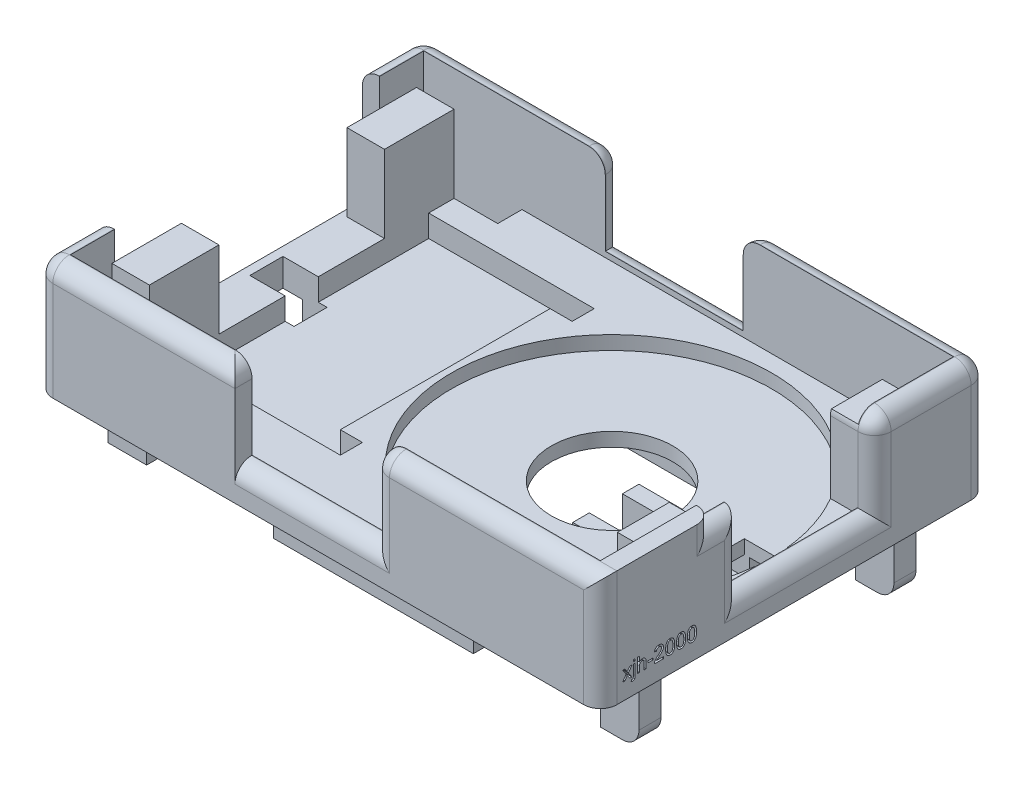
SolidWorks part; units mm, degrees
note: The reader was unsure of these and kept them because the rebuilt part matched: shared geometry of "草图1<4>".
material "PP 共聚物"
ref_plane "前视基准面" through (0, 0, 0) normal (0, 0, 1) x (1, 0, 0)
ref_plane "上视基准面" through (0, 0, 0) normal (0, 1, 0) x (1, 0, 0)
ref_plane "右视基准面" through (0, 0, 0) normal (1, 0, 0) x (0, 0, -1)
sketch "草图1" plane through (0, 0, 0) normal (0, 1, 0) x (1, 0, 0)
  line L5 (48.1, -32.1) -> (-48.1, -32.1)
  line L6 (48.1, -32.1) -> (48.1, 32.1)
  line L7 (48.1, 32.1) -> (-48.1, 32.1)
  line L8 (-48.1, -32.1) -> (-48.1, 32.1)
  line L9 (48.1, -32.1) -> (-48.1, 32.1) construction
  line L10 (48.1, 32.1) -> (-48.1, -32.1) construction
  point P0 (0, 0)
  dimension "D1" = 96.2
  dimension "D2" = 64.2
extrude "凸台-拉伸1基本面" add sketch "草图1" along normal blind 5 contours L6 L5 L8 L7
sketch "超声空间" plane through (0, 0, 0) normal (0, -1, 0) x (1, 0, 0)
  line L1 (-50.5, 24) -> (-44.5, 24)
  line L2 (-50.5, 24) -> (-50.5, -24)
  line L3 (-50.5, -24) -> (-44.5, -24)
  line L4 (-44.5, 24) -> (-44.5, -24)
  line L5 (-59.6476, 0) -> (64.1438, 0) construction
  dimension "D1" = 48
  dimension "D2" = 6
sketch "草图4" plane through (0, 0, 0) normal (0, 1, 0) x (1, 0, 0)
  line L0 (-71.4213, 0) -> (77.6532, 0) construction
  line L1 (41.1, 25.1) -> (48.1, 25.1)
  line L2 (-48.1, 25.1) -> (-41.1, 25.1)
  line L3 (-48.1, 25.1) -> (-48.1, 21.1)
  line L4 (-48.1, 21.1) -> (-41.1, 21.1)
  line L5 (-41.1, 25.1) -> (-41.1, 21.1)
  line L6 (41.1, 25.1) -> (41.1, 21.1)
  line L7 (41.1, 21.1) -> (48.1, 21.1)
  line L8 (48.1, 25.1) -> (48.1, 21.1)
  line L9 (48.1, -25.1) -> (48.1, -21.1)
  line L10 (41.1, -21.1) -> (48.1, -21.1)
  line L11 (41.1, -25.1) -> (41.1, -21.1)
  line L12 (-41.1, -25.1) -> (-41.1, -21.1)
  line L13 (-48.1, -21.1) -> (-41.1, -21.1)
  line L14 (-48.1, -25.1) -> (-48.1, -21.1)
  line L15 (-48.1, -25.1) -> (-41.1, -25.1)
  line L16 (41.1, -25.1) -> (48.1, -25.1)
  line L17 (48.1, 32.1) -> (-48.1, 32.1) construction
  line L18 (-48.1, -32.1) -> (-48.1, 32.1) construction
  line L19 (48.1, -32.1) -> (48.1, 32.1) construction
  line L20 (18.1, -25.1) -> (18.1, -21.1)
  line L21 (-18.1, 25.1) -> (18.1, 25.1)
  line L22 (-18.1, 25.1) -> (-18.1, 21.1)
  line L23 (-18.1, 21.1) -> (18.1, 21.1)
  line L24 (18.1, 25.1) -> (18.1, 21.1)
  line L25 (-18.1, -21.1) -> (18.1, -21.1)
  line L26 (-18.1, -25.1) -> (-18.1, -21.1)
  line L27 (-18.1, -25.1) -> (18.1, -25.1)
  dimension "D1" = 4
  dimension "D2" = 7
  dimension "D3" = 23
  dimension "D4" = 23
  dimension "D5" = 7
  dimension "D6" = 7
extrude "凸台-拉伸3-舵机支撑" add sketch "草图4" against normal blind 12
sketch "草图5" plane through (0, 5, 0) normal (0, 1, 0) x (1, 0, 0)
  line L0 (-67.8133, 0) -> (64.4513, 0) construction
  line L2 (-44.9, 27.6) -> (-38.1, 27.6)
  line L3 (-44.9, 27.6) -> (-44.9, 15)
  line L4 (-44.9, 15) -> (-38.1, 15)
  line L5 (-38.1, 27.6) -> (-38.1, 15)
  line L13 (-38.1, -27.6) -> (-38.1, -15)
  line L14 (-44.9, -15) -> (-38.1, -15)
  line L15 (-44.9, -27.6) -> (-44.9, -15)
  line L16 (-44.9, -27.6) -> (-38.1, -27.6)
  line L17 (-48.1, -32.1) -> (-48.1, 32.1) construction
  line L18 (48.1, 32.1) -> (-48.1, 32.1) construction
  line L31 (48.1, -32.1) -> (48.1, 32.1) construction
  line L42 (43.1, -14.6) -> (48.1, -14.6)
  line L43 (48.1, -24) -> (48.1, -14.6)
  line L44 (43.1, -24) -> (48.1, -24)
  line L45 (43.1, -24) -> (43.1, -14.6)
  line L46 (48.1, -32.1) -> (-48.1, -32.1) construction
  line L47 (43.1, 24) -> (43.1, 14.6)
  line L48 (43.1, 24) -> (48.1, 24)
  line L49 (48.1, 24) -> (48.1, 14.6)
  line L50 (43.1, 14.6) -> (48.1, 14.6)
  dimension "D1" = 3.2
  dimension "D2" = 10
  dimension "D3" = 4.5
  dimension "D4" = 30
  dimension "D5" = 5
  dimension "D6" = 9.4
  dimension "D7" = 8.1
extrude "凸台-拉伸4-板子螺丝支撑" add sketch "草图5" along normal blind 14
sketch "草图12" plane through (0, 0, 0) normal (0, -1, 0) x (1, 0, 0)
  line L0 (-56.5877, 0) -> (64.1716, 0) construction
  line L1 (0, 37.482) -> (0, -42.0761) construction
  line L12 (-41, 6) -> (-18, 6)
  line L13 (-41, 6) -> (-41, 3)
  line L14 (-41, 3) -> (-18, 3)
  line L15 (-18, 6) -> (-18, 3)
  line L16 (-41, -3) -> (-18, -3)
  line L17 (-18, -6) -> (-18, -3)
  line L18 (-41, -6) -> (-18, -6)
  line L19 (-41, -6) -> (-41, -3)
  line L20 (17, 6) -> (17, 3)
  line L21 (17, 6) -> (40, 6)
  line L22 (40, 6) -> (40, 3)
  line L23 (17, 3) -> (40, 3)
  line L24 (17, -3) -> (40, -3)
  line L25 (40, -6) -> (40, -3)
  line L26 (17, -6) -> (40, -6)
  line L27 (17, -6) -> (17, -3)
  dimension "D2" = 6
  dimension "D3" = 3
  dimension "D4" = 23
  dimension "D5" = 18
  dimension "D6" = 23
  dimension "D7" = 3
  dimension "D8" = 3
  dimension "D9" = 17
  dimension "D1" = 2
extrude "凸台-拉伸8-理线" add sketch "草图12" along normal blind 10
extrude "拉伸-薄壁" add sketch "草图1<4>" along normal offset from surface (21 mm away) 2 thin up to face at (-41.5, 19, -21.3) offset beyond the face yes thin type two direction wall 3 second wall 0.1
sketch "草图1<4>" plane through (0, 0, 0) normal (0, 1, 0) x (1, 0, 0) same geometry as "草图1"
sketch "草图13" plane through (0, 0, 0) normal (0, -1, 0) x (1, 0, 0)
  line L1 (39.1, 3) -> (47.1, 3)
  line L2 (39.1, 3) -> (39.1, -3)
  line L3 (39.1, -3) -> (47.1, -3)
  line L4 (47.1, 3) -> (47.1, -3)
  line L6 (51.1, 35.1) -> (51.1, -35.1) construction
  line L7 (-58, 0) -> (66.2478, 0) construction
  line L14 (-44.5, 3) -> (-36.5, 3)
  line L15 (-44.5, 3) -> (-44.5, -3)
  line L16 (-44.5, -3) -> (-36.5, -3)
  line L17 (-36.5, 3) -> (-36.5, -3)
  line L18 (-41, 3) -> (-18, 3) construction
  dimension "D1" = 8
  dimension "D2" = 6
  dimension "D3" = 4
  dimension "D4" = 8
extrude "切除-拉伸-理线" cut sketch "草图13" against normal up to next
sketch "草图21" plane through (0, 0, 35.1) normal (0, 0, 1) x (1, 0, 0)
  line L0 (-51.1, 21) -> (51.1, 21) construction
  line L1 (-15.1, 21) -> (9.9, 21)
  line L2 (-15.1, 21) -> (-15.1, 6)
  line L3 (-15.1, 6) -> (9.9, 6)
  line L4 (9.9, 21) -> (9.9, 6)
  line L5 (-51.1, 0) -> (51.1, 0) construction
  line L6 (-51.1, 21) -> (-51.1, 0) construction
  dimension "D1" = 25
  dimension "D2" = 6
  dimension "D3" = 36
extrude "切除-拉伸-侧边红外" cut sketch "草图21" against normal through all
sketch "草图22" plane through (51.1, 0, 0) normal (1, 0, 0) x (0, 0, -1)
  line L0 (-35.1, 21) -> (35.1, 21) construction
  line L1 (-14.6, 21) -> (-14.6, 19)
  line L2 (-14.6, 19) -> (-9.6, 19)
  line L3 (-9.6, 19) -> (-9.6, 6)
  line L4 (-9.6, 6) -> (14.6, 6)
  line L5 (14.6, 6) -> (14.6, 21)
  line L6 (14.6, 21) -> (-14.6, 21)
  line L7 (0, 0) -> (0, 26.7985) construction
  line L8 (-35.1, 0) -> (35.1, 0) construction
  line L9 (35.1, 21) -> (35.1, 0) construction
  line L10 (-35.1, 21) -> (-35.1, 0) construction
  point P16 (-9.6, 12.5)
  dimension "D1" = 20.5
  dimension "D2" = 20.5
  dimension "D3" = 6
  dimension "D4" = 25.5
  dimension "D5" = 2
extrude "切除-拉伸-尾部红外" cut sketch "草图22" against normal up to next
sketch "草图25" plane through (51.1, 0, 0) normal (1, 0, 0) x (0, 0, -1)
  line L0 (-35.1, 21) -> (-35.1, 0) construction
  line L1 (-35.1, 0) -> (35.1, 0) construction
  text T0 "xjh-2000" height in points 10
  point P5 (-30.2298, 8.4333)
  dimension "D1" = 4
  dimension "D2" = 3
extrude "切除-拉伸-自我介绍" cut sketch "草图25" against normal blind 1.5
sketch "草图20" plane through (0, 5, 0) normal (0, 1, 0) x (1, 0, 0)
  line L2 (30.1917, 32) -> (44.5, 32)
  line L3 (30.1917, 32) -> (30.1917, 27.6)
  line L4 (30.1917, 27.6) -> (44.5, 27.6)
  line L5 (44.5, 32) -> (44.5, 27.6)
  line L6 (0, 37.255) -> (0, -43.0013) construction
  line L7 (0, -37.482) -> (0, 42.0761) construction
  line L8 (-58.1518, 0) -> (69.3057, 0) construction
  line L9 (-30.1917, 27.6) -> (-44.5, 27.6)
  line L10 (-44.5, 32) -> (-44.5, 27.6)
  line L11 (-30.1917, 32) -> (-44.5, 32)
  line L12 (-30.1917, 32) -> (-30.1917, 27.6)
  line L13 (30.1917, -27.6) -> (44.5, -27.6)
  line L14 (44.5, -32) -> (44.5, -27.6)
  line L15 (30.1917, -32) -> (44.5, -32)
  line L16 (30.1917, -32) -> (30.1917, -27.6)
  line L17 (-30.1917, -32) -> (-30.1917, -27.6)
  line L18 (-30.1917, -32) -> (-44.5, -32)
  line L19 (-44.5, -32) -> (-44.5, -27.6)
  line L20 (-30.1917, -27.6) -> (-44.5, -27.6)
  line L21 (-44.9, -27.6) -> (-38.1, -27.6) construction
  line L22 (48, -14.6) -> (48, 14.6) construction
  line L23 (48, 32) -> (-48, 32) construction
  line L26 (-38.1, 27.6) -> (-44.9, 27.6) construction
  dimension "D1" = 3.5
  dimension "D4" = 0
extrude "切除-拉伸_舵机插头空间" cut sketch "草图20" against normal up to next
sketch "草图26" plane through (0, 0, 0) normal (0, -1, 0) x (1, 0, 0)
  line L0 (-51.1, -35.1) -> (-51.1, 35.1) construction
  line L1 (-51.1, 24) -> (-46.1, 24)
  line L2 (-51.1, 24) -> (-51.1, -24)
  line L3 (-51.1, -24) -> (-46.1, -24)
  line L4 (-46.1, 24) -> (-46.1, -24)
  line L6 (-59.6476, 0) -> (71.5879, 0) construction
  dimension "D1" = 5
  dimension "D2" = 48
extrude "切除-拉伸-超声空间" cut sketch "草图26" against normal through all and the other way through all
fillet "圆角" radius 3 45 edges at (45.55, 19, -14.6) (-41, -10, 4.5) (-18, -10, 4.5) (-41, -10, -4.5) (-18, -10, -4.5) (17, -10, 4.5) (40, -10, 4.5) (17, -10, -4.5) (40, -10, -4.5) (48.1, 0, 23.1) (48.1, 0, -23.1) (51.1, 10.5, -35.1) (51.1, 10.5, 35.1) (-51.1, 10.5, 35.1) (-51.1, 10.5, -35.1) (30.5, 21, -35.1) (-51.1, 21, -29.55) (-33.1, 21, 35.1) (48.1, -12, -23.1) (-33.1, 21, -35.1) (30.5, 21, 35.1) (9.9, 21, 33.55) (-15.1, 21, 33.55) (-15.1, 21, -33.55) (-2.6, 6, -35.1) (-15.1, 13.5, -35.1) (9.9, 13.5, -35.1) (9.9, 21, -33.55) (44.6, 0, -21.1) (-2.6, 6, 35.1) (9.9, 13.5, 35.1) (48, 20, -14.6) (49.55, 21, -14.6) (51.1, 20, 14.6) (51.1, 19, 12.1) (51.1, 12.5, 9.6) (51.1, 6, -2.5) (51.1, 13.5, -14.6) (48.1, -12, 23.1) (44.6, 0, 21.1) (-43.6, 0, 21.1) (0, 0, -21.1) (-51.1, 21, 29.55) (-43.6, 0, -21.1) (0, 0, 21.1)
sketch "草图27" plane through (0, 5, 0) normal (0, 1, 0) x (1, 0, 0)
  line L0 (-59.6476, 0) -> (72.0758, 0) construction
  line L1 (-59.6476, 0) -> (64.1438, 0) construction
  line L2 (-12.1, -19) -> (-8.1, -19)
  line L3 (-12.1, 23) -> (-8.1, 23)
  line L4 (-38.1, 15) -> (-38.1, 27.6) construction
  line L5 (-38.1, 23) -> (-12.1, 23)
  line L6 (-38.1, 23) -> (-38.1, -23)
  line L7 (-38.1, -23) -> (-12.1, -23)
  line L10 (-12.1, 19) -> (-8.1, 19)
  line L11 (-8.1, 23) -> (-8.1, 19)
  line L12 (-8.1, -23) -> (-8.1, -19)
  line L13 (-12.1, -23) -> (-8.1, -23)
  line L15 (-12.1, -19) -> (-12.1, 19)
  circle A0 centre (18.0433, 0) radius 29 construction
  circle A1 centre (18.0433, 0) radius 9
  dimension "D1" = 58
  dimension "D2" = 26
  dimension "D4" = 18
  dimension "D3" = 46
  dimension "D5" = 4
  dimension "D6" = 4
  dimension "D7" = 38
extrude "切除-拉伸-电池槽" cut sketch "草图27" against normal blind 4
sketch "草图29" plane through (0, 5, 0) normal (0, 1, 0) x (1, 0, 0)
  circle A1 centre (18.0433, 0.0894) radius 11
extrude "切除-拉伸-喇叭中心槽" cut sketch "草图29" against normal blind 6.5
sketch "草图30" plane through (0, 5, 0) normal (0, 1, 0) x (1, 0, 0)
  circle A0 centre (18.0433, 0) radius 29 construction
  circle A1 centre (18.0433, 0) radius 29
extrude "切除-拉伸-喇叭外圆槽" cut sketch "草图30" against normal blind 2.5
equation "\"10、\"=5"
